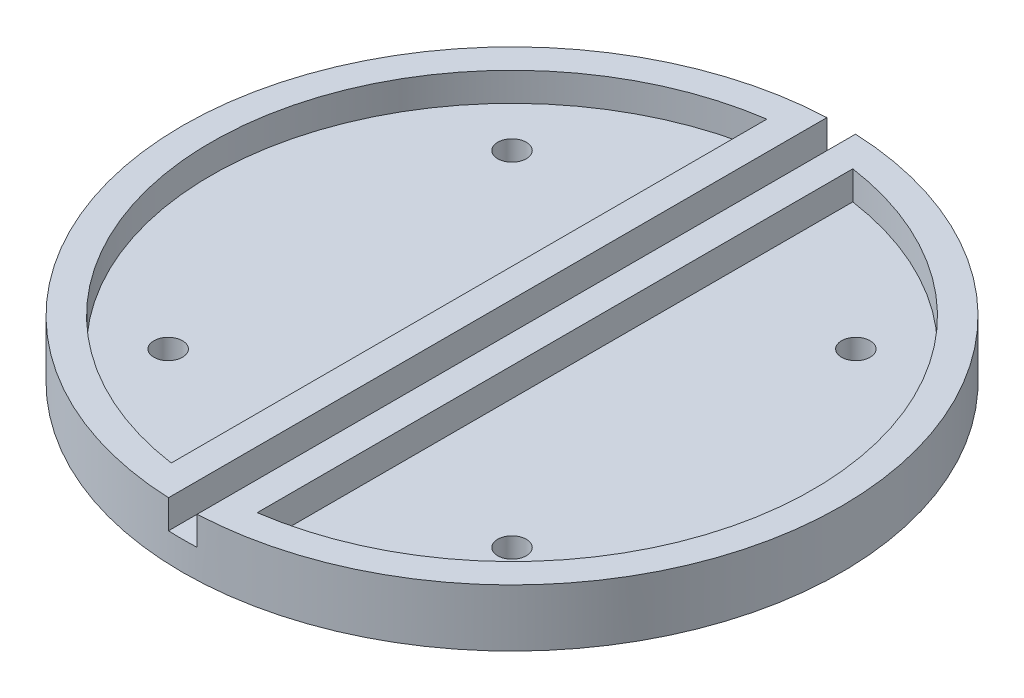
SolidWorks part; units mm, degrees
material "ABS"
ref_plane "Front Plane" through (0, 0, 0) normal (0, 0, 1) x (1, 0, 0)
ref_plane "Top Plane" through (0, 0, 0) normal (0, 1, 0) x (1, 0, 0)
ref_plane "Right Plane" through (0, 0, 0) normal (1, 0, 0) x (0, 0, -1)
sketch "Sketch5" plane through (0, 0, 0) normal (0, 1, 0) x (1, 0, 0)
  circle A0 centre (0, 0) radius 73.025
  circle A1 centre (38.1, 38.1) radius 3.175
  circle A2 centre (38.1, -38.1) radius 3.175
  circle A3 centre (-38.1, 38.1) radius 3.175
  circle A4 centre (-38.1, -38.1) radius 3.175
extrude "PlateBase" add sketch "Sketch5" along normal blind 6.35
sketch "Sketch6" plane through (0, 6.35, 0) normal (0, 1, 0) x (1, 0, 0)
  line L1 (3.175, 0) -> (3.175, 72.9559)
  line L3 (3.175, 0) -> (3.175, -72.9559)
  line L4 (0, 0) -> (3.175, 0)
  line L5 (-3.175, 0) -> (-3.175, 72.9559)
  line L6 (-9.525, 0) -> (-9.525, 72.4011)
  line L7 (-9.525, 0) -> (-9.525, -72.4011)
  line L8 (-3.175, 0) -> (-3.175, -72.9559)
  line L9 (9.525, 0) -> (9.525, 72.4011)
  line L10 (9.525, 0) -> (9.525, -72.4011)
  circle A0 centre (0, 0) radius 73.025 construction
  circle M4 centre (0, 0) radius 73.025
extrude "PlateTop" add sketch "Sketch6" along normal blind 6.35 contours L8 L5 L6 L7 M4 | L10 L9 L1 L3 M4 region at (6.346, 6.35, 0) region at (-6.346, 6.35, 0)
sketch "Sketch9" plane through (0, 6.35, 0) normal (0, 1, 0) x (1, 0, 0)
  circle A0 centre (0, 0) radius 66.675
  circle A1 centre (0, 0) radius 73.025
extrude "PlateWalls" add sketch "Sketch9" along normal blind 6.35
sketch "Sketch11" plane through (0, 12.7, 0) normal (0, 1, 0) x (1, 0, 0)
  line L0 (-3.175, 66.5994) -> (-3.175, 72.9559)
  line L1 (3.175, 66.5994) -> (3.175, 72.9559)
  line L2 (-3.175, 66.5994) -> (3.175, 66.5994)
  circle A0 centre (0, 0) radius 73.025 construction
  arc A1 (-3.175, 72.9559) -> (3.175, 72.9559) centre (0, 0) cw
extrude "TopSlotCut" cut sketch "Sketch11" against normal blind 6.35
sketch "Sketch12" plane through (0, 12.7, 0) normal (0, 1, 0) x (1, 0, 0)
  line L0 (-3.175, -66.5994) -> (-3.175, -72.9559)
  line L1 (3.175, -66.5994) -> (3.175, -72.9559)
  line L2 (-3.175, -66.5994) -> (3.175, -66.5994)
  arc A0 (-3.175, 72.9559) -> (3.175, 72.9559) centre (0, 0) ccw construction
  arc A1 (3.175, -72.9559) -> (-3.175, -72.9559) centre (0, 0) cw
extrude "BottomSlotCut" cut sketch "Sketch12" against normal blind 6.35
